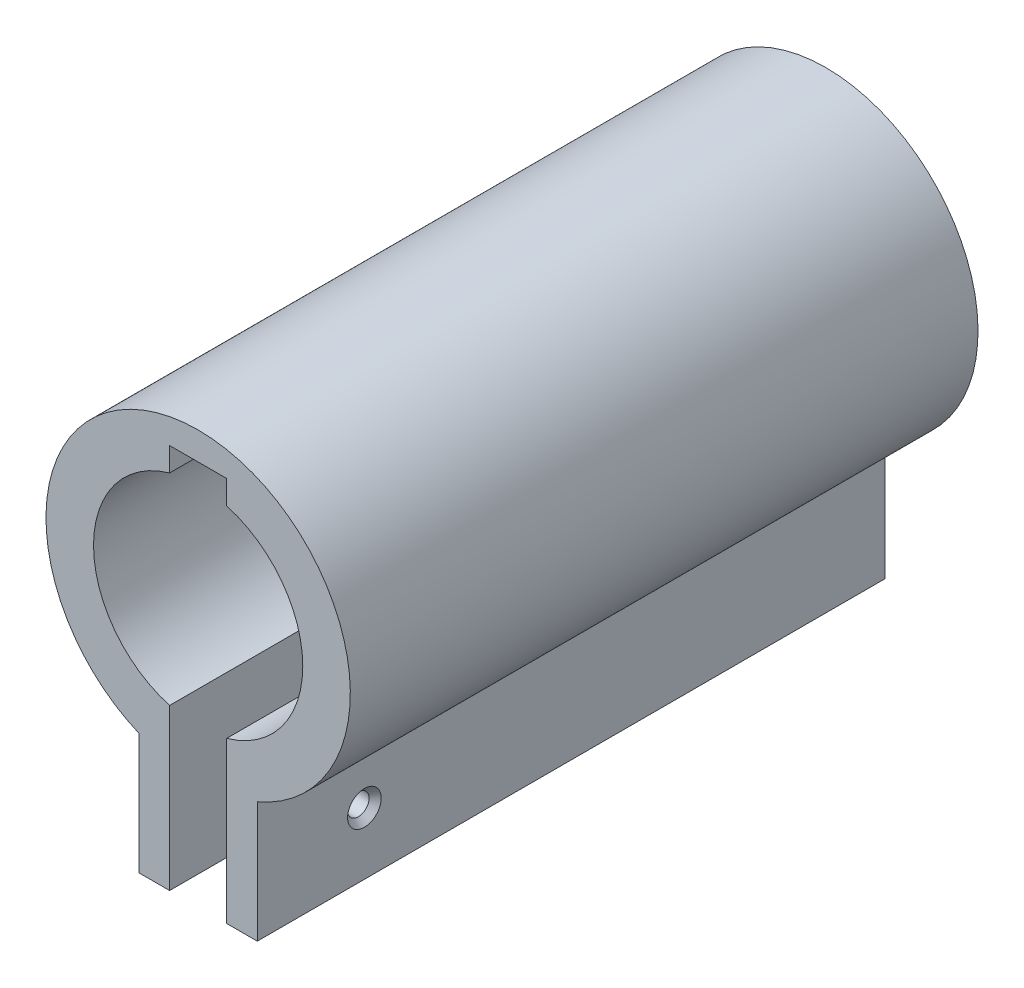
SolidWorks part; units mm, degrees
ref_plane "Front Plane" through (0, 0, 0) normal (0, 0, 1) x (1, 0, 0)
ref_plane "Top Plane" through (0, 0, 0) normal (0, 1, 0) x (1, 0, 0)
ref_plane "Right Plane" through (0, 0, 0) normal (1, 0, 0) x (0, 0, -1)
sketch "Sketch1" plane through (0, 0, 0) normal (0, 0, 1) x (1, 0, 0)
  circle A0 centre (0, 0) radius 11
  circle A1 centre (0, 0) radius 16
  dimension "D1" = 22
  dimension "D2" = 5
extrude "Boss-Extrude1" add sketch "Sketch1" along normal blind 33 and the other way blind 33
sketch "Sketch2" plane through (0, 0, 33) normal (0, 0, 1) x (1, 0, 0)
  line L0 (-3, 10.583) -> (-3, 13.083)
  line L2 (3, 13.083) -> (3, 10.583)
  line L3 (0, 0) -> (0, 13.083) construction
  line L4 (-3, 13.083) -> (0, 13.083)
  line L5 (0, 13.083) -> (3, 13.083)
  line L6 (-3, 10.583) -> (3, 10.583)
  circle A3 centre (0, 0) radius 11 construction
  point P1 (0, 0)
  dimension "D1" = 3
  dimension "D2" = 3
  dimension "D3" = 2.5
  dimension "D4" = 2.5
extrude "Cut-Extrude1" cut sketch "Sketch2" against normal blind 33
mirror "Mirror2" about plane through (0, 0, 0) normal (0, 0, -1) of "Cut-Extrude1"
sketch "Sketch3" plane through (0, 0, 33) normal (0, 0, 1) x (1, 0, 0)
  line L0 (-3, -10.583) -> (-3, -15.7162)
  line L1 (-3, -15.7162) -> (-3, -10.583)
  line L2 (3, -10.583) -> (3, -15.7162)
  line L3 (-3, -10.583) -> (3, -10.583)
  line L4 (-3, -15.7162) -> (-3, -27.4422)
  line L5 (-3, -27.4422) -> (-6.2184, -27.4422)
  line L6 (-6.2184, -27.4422) -> (-6.2184, -14.7422)
  line L7 (-6.2184, -14.7422) -> (-3, -14.7422)
  line L8 (3, -15.7162) -> (3, -27.4422)
  line L9 (3, -27.4422) -> (6.2184, -27.4422)
  line L10 (6.2184, -27.4422) -> (6.2184, -14.7422)
  line L11 (6.2184, -14.7422) -> (3, -14.7422)
  arc A0 (-3, 10.583) -> (3, 10.583) centre (0, 0) ccw construction
  circle A1 centre (0, 0) radius 16 construction
  circle M6 centre (0, 0) radius 16
  dimension "D1" = 12.7
extrude "Boss-Extrude2" add sketch "Sketch3" against normal through all contours L6 L5 L4 M6 | L9 L10 L8 M6 region at (-4.6307, -21.3633, 33) region at (4.6307, -21.3633, 33)
sketch "Sketch4" plane through (0, 0, 33) normal (0, 0, 1) x (1, 0, 0)
  line L0 (-3, -10.583) -> (-3, -16.2715)
  line L1 (-3, -10.583) -> (3, -10.583)
  line L2 (3, -10.583) -> (3, -15.7162)
  line L3 (-3, -15.7162) -> (-3, -27.4422) construction
  line L4 (-3, -16.2715) -> (3, -16.2715)
  line L5 (3, -15.7162) -> (3, -27.4422) construction
  line L6 (3, -16.2715) -> (3, -15.7162)
  arc A0 (-3, 10.583) -> (3, 10.583) centre (0, 0) ccw construction
extrude "Cut-Extrude4" cut sketch "Sketch4" against normal through all
sketch "Sketch6" plane through (6.2184, 0, 0) normal (1, 0, 0) x (0, 0, -1)
  circle A0 centre (-21.7389, -20.9335) radius 1.42
  dimension "D1" = 2.84
hole_wizard "#4-40 Tapped Hole2" positions "Sketch7" profile "Sketch8" tap size "#4-40" standard "ANSI Inch" end condition through all
sketch "Sketch7" plane through (6.2184, 0, 0) normal (1, 0, 0) x (0, 0, -1)
  point P0 (-21.7389, -20.9335)
sketch "Sketch8" plane through (6.2184, -20.9335, 21.7389) normal (0, 1, 0) x (0, 0, -1)
  line L0 (0, 0) -> (0, 22.2184)
  line L1 (0, 22.2184) -> (1.1303, 22.2184)
  line L2 (1.1303, 22.2184) -> (1.1303, 0.635)
  line L3 (1.1303, 0.635) -> (1.7653, 0)
  line L5 (1.7653, 0) -> (0, 0)
  line L6 (-1.1303, 0.635) -> (-1.7653, 0) construction
  line L11 (0, -6.35) -> (0, 107.95) construction
  dimension "Thru Tap Drill Dia." = 2.2606
  dimension "Thru Tap Drill Depth" = 22.2184
  dimension "Near C'Sink Dia." = 3.5306
  dimension "Near C'Sink Angle" = 90
cosmetic thread "Hole Thread2" parameters "D2"=2.8448
